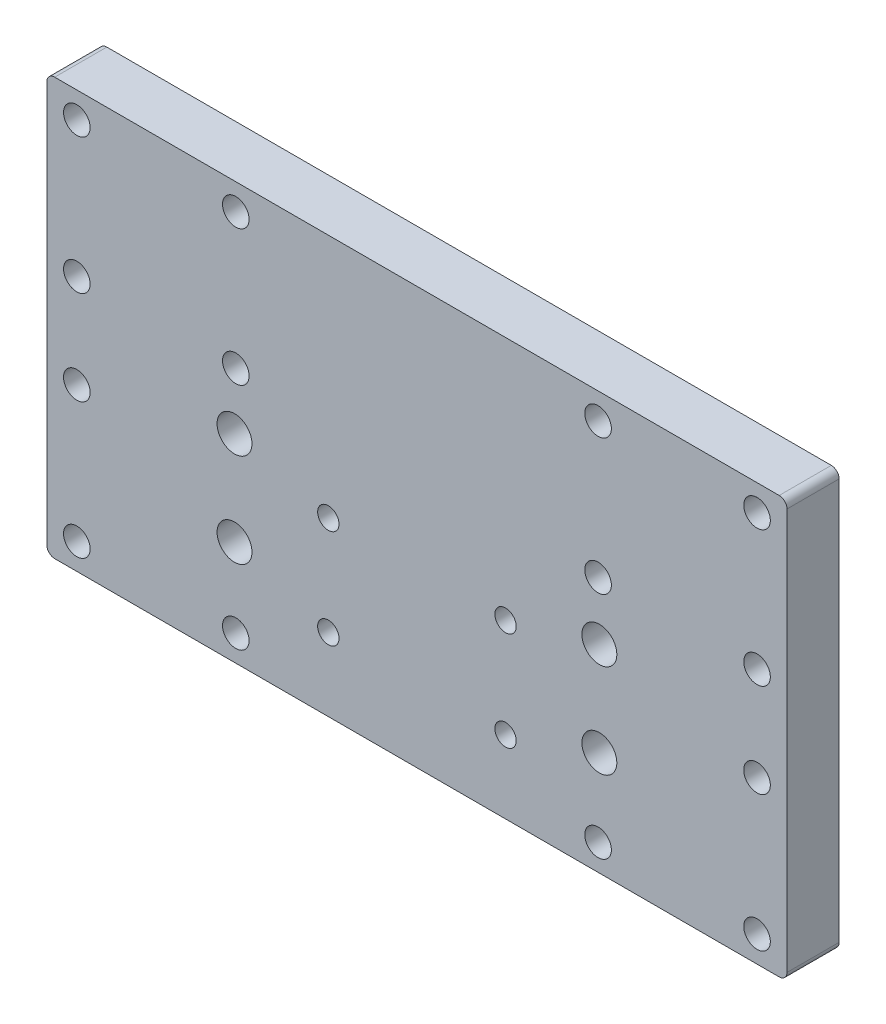
SolidWorks part; units mm, degrees
ref_plane "Front Plane" through (0, 0, 0) normal (0, 0, 1) x (1, 0, 0)
ref_plane "Top Plane" through (0, 0, 0) normal (0, 1, 0) x (1, 0, 0)
ref_plane "Right Plane" through (0, 0, 0) normal (1, 0, 0) x (0, 0, -1)
sketch "Sketch1" plane through (0, 0, 0) normal (0, 0, 1) x (1, 0, 0)
  line L1 (-71, -40) -> (71, -40)
  line L2 (-71, -40) -> (-71, 40)
  line L3 (-71, 40) -> (71, 40)
  line L4 (71, -40) -> (71, 40)
  line L5 (-71, -40) -> (71, 40) construction
  line L6 (-71, 40) -> (71, -40) construction
  point P0 (0, 0)
  dimension "D1" = 80
  dimension "D2" = 142
extrude "Boss-Extrude1" add sketch "Sketch1" along normal mid plane 10
sketch "Sketch2" plane through (0, 0, 5) normal (0, 0, 1) x (1, 0, 0)
  line L3 (-65.25, 40) -> (-65.25, -40)
  line L4 (-65.25, 40) -> (-65.25, -40) construction
  line L6 (65.25, -40) -> (65.25, 40)
  line L7 (65.25, -40) -> (65.25, 40) construction
  line L13 (-34.75, 40) -> (-34.75, -40)
  line L14 (-34.75, 40) -> (-34.75, -40) construction
  line L16 (34.75, -40) -> (34.75, 40)
  line L18 (34.75, -40) -> (34.75, 40) construction
  line L20 (71, 35) -> (-71, 35)
  line L21 (71, 35) -> (-71, 35) construction
  line L23 (-71, -35) -> (71, -35)
  line L24 (-71, -35) -> (71, -35) construction
  line L26 (71, 9) -> (-71, 9)
  line L27 (71, 9) -> (-71, 9) construction
  line L29 (-71, -9) -> (71, -9)
  line L30 (-71, -9) -> (71, -9) construction
  circle A0 centre (-65.25, 35) radius 2.55
  circle A1 centre (-34.75, 35) radius 2.55
  circle A2 centre (-34.75, 9) radius 2.55
  circle A3 centre (-65.25, 9) radius 2.55
  circle A4 centre (65.25, 35) radius 2.55
  circle A5 centre (65.25, 9) radius 2.55
  circle A6 centre (34.75, 9) radius 2.55
  circle A7 centre (34.75, 35) radius 2.55
  circle A8 centre (-65.25, -9) radius 2.55
  circle A10 centre (-34.75, -35) radius 2.55
  circle A11 centre (-65.25, -35) radius 2.55
  circle A13 centre (65.25, -9) radius 2.55
  circle A14 centre (65.25, -35) radius 2.55
  circle A15 centre (34.75, -35) radius 2.55
  dimension "D9" = 5.1
  dimension "D10" = 5.1
  dimension "D11" = 5.1
  dimension "D12" = 5.1
  dimension "D13" = 5.1
  dimension "D14" = 5.1
  dimension "D15" = 5.1
  dimension "D16" = 5.1
  dimension "D17" = 5.1
  dimension "D18" = 5.1
  dimension "D20" = 5.1
  dimension "D21" = 5.1
  dimension "D23" = 5.1
  dimension "D24" = 5.1
  dimension "D1" = 5.75
  dimension "D2" = 5.75
  dimension "D3" = 36.25
  dimension "D4" = 36.25
  dimension "D5" = 5
  dimension "D6" = 5
  dimension "D7" = 31
  dimension "D8" = 31
extrude "Cut-Extrude1" cut sketch "Sketch2" against normal through all
sketch "Sketch3" plane through (0, 0, 5) normal (0, 0, 1) x (1, 0, 0)
  line L0 (-71, -40) -> (71, -40) construction
  line L1 (-17, -7) -> (17, -7) construction
  line L2 (-17, -7) -> (-17, -26) construction
  line L3 (-17, -26) -> (17, -26) construction
  line L4 (17, -7) -> (17, -26) construction
  line L5 (-17, -7) -> (17, -26) construction
  line L6 (-17, -26) -> (17, -7) construction
  line L7 (0, 40) -> (0, -40) construction
  line L8 (71, 40) -> (-71, 40) construction
  circle A0 centre (-17, -7) radius 2.05
  circle A1 centre (-17, -26) radius 2.05
  circle A2 centre (17, -26) radius 2.05
  circle A3 centre (17, -7) radius 2.05
  point P0 (0, 0)
  dimension "D3" = 4.1
  dimension "D4" = 4.1
  dimension "D5" = 4.1
  dimension "D6" = 4.1
  dimension "D1" = 34
  dimension "D2" = 19
  dimension "D7" = 14
  dimension "D8" = 17
extrude "Cut-Extrude2" cut sketch "Sketch3" against normal through all
sketch "Sketch4" plane through (0, 0, 5) normal (0, 0, 1) x (1, 0, 0)
  line L0 (0, 40) -> (0, -40) construction
  line L1 (-35, -20) -> (35, -20) construction
  line L2 (-35, -20) -> (-35, -2) construction
  line L3 (-35, -2) -> (35, -2) construction
  line L4 (35, -20) -> (35, -2) construction
  line L5 (-35, -20) -> (35, -2) construction
  line L6 (-35, -2) -> (35, -20) construction
  line L7 (71, 40) -> (-71, 40) construction
  line L8 (-71, -40) -> (71, -40) construction
  circle A0 centre (-35, -2) radius 3.35
  circle A1 centre (35, -2) radius 3.35
  circle A2 centre (35, -20) radius 3.35
  circle A3 centre (-35, -20) radius 3.35
  point P0 (0, -11)
  dimension "D3" = 6.7
  dimension "D4" = 6.7
  dimension "D5" = 6.7
  dimension "D6" = 6.7
  dimension "D1" = 70
  dimension "D2" = 18
  dimension "D7" = 20
extrude "Cut-Extrude3" cut sketch "Sketch4" against normal through all
fillet "Fillet1" radius 1.5 4 edges at (-71, -40, 0) (71, -40, 0) (71, 40, 0) (-71, 40, 0)
equation "\"D4@Sketch3\"=\"D3@Sketch3\""
equation "\"D5@Sketch3\"=\"D3@Sketch3\""
equation "\"D6@Sketch3\"=\"D3@Sketch3\""
equation "\"D4@Sketch4\"=\"D3@Sketch4\""
equation "\"D5@Sketch4\"=\"D3@Sketch4\""
equation "\"D6@Sketch4\"=\"D3@Sketch4\""
equation "\"D10@Sketch2\"=\"D24@Sketch2\""
equation "\"D16@Sketch2\"=\"D24@Sketch2\""
